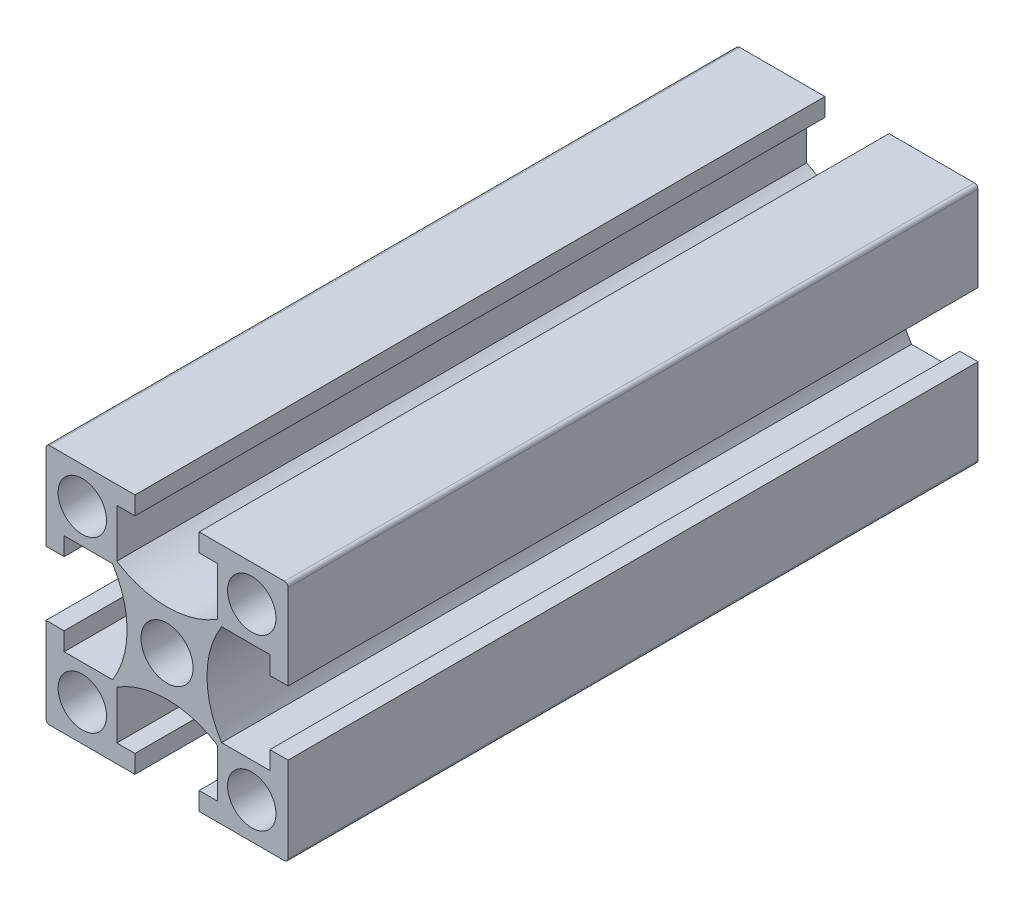
SolidWorks part; units mm, degrees
material "3.0255 (EN-AW 1350A)"
ref_plane "정면" through (0, 0, 0) normal (0, 0, 1) x (1, 0, 0)
ref_plane "윗면" through (0, 0, 0) normal (0, 1, 0) x (1, 0, 0)
ref_plane "우측면" through (0, 0, 0) normal (1, 0, 0) x (0, 0, -1)
sketch "스케치1" plane through (0, 0, 0) normal (0, 0, 1) x (1, 0, 0)
  line L0 (0, 32.0265) -> (0, -31.6588) construction
  line L1 (-10, 10) -> (-10, -10)
  line L2 (-10, 10) -> (10, 10)
  line L3 (-10, 2.65) -> (-8.5, 2.65)
  line L4 (13.6618, 0) -> (-11.6993, 0) construction
  line L5 (-8.5, 2.65) -> (-8.5, 4.15)
  line L6 (-8.5, 4.15) -> (-4.5032, 4.15)
  line L7 (-10, -2.65) -> (-8.5, -2.65)
  line L8 (-8.5, -2.65) -> (-8.5, -4.15)
  line L9 (-8.5, -4.15) -> (-4.5032, -4.15)
  line L10 (-10, -10) -> (10, -10)
  line L11 (10, 10) -> (10, -10)
  circle A0 centre (-7, 7) radius 2
  circle A1 centre (-7, -7) radius 2
  arc A2 (-4.5032, 4.15) -> (-4.5032, -4.15) centre (-11.0587, 0) cw
  circle A3 centre (0, 0) radius 2.15
  circle A4 centre (7, 7) radius 2
  circle A5 centre (7, -7) radius 2
  point P21 (-10, 0)
  point P23 (-3.3, 0)
  point P31 (0, -10)
  point P32 (0, 10)
  dimension "D3" = 4
  dimension "D9" = 6.7
  dimension "D10" = 4.3
  dimension "D11" = 7.7587
  dimension "D1" = 20
  dimension "D2" = 20
  dimension "D4" = 14
  dimension "D5" = 14
  dimension "D6" = 5.3
  dimension "D7" = 8.3
  dimension "D8" = 1.5
extrude "보스-돌출1" add sketch "스케치1" along normal blind 57 contours A0 | A4 | A3 | A5 | A1 | A2 L6 L5 L3 L1 L7 L8 L9 | L2 L11 L10 L1 region at (-6.6069, 0, 0) region at (-7, 7, 0) region at (-7, -7, 0) region at (0, 0, 0) region at (7, 7, 0) region at (7, -7, 0)
extrude "컷-돌출1" cut sketch "스케치1<3>" along normal up to next contours A2 L6 L5 L3 L1 L7 L8 L9 region at (-6.6069, 0, 0)
sketch "스케치1<3>" plane through (0, 0, 0) normal (0, 0, 1) x (1, 0, 0) same geometry as "스케치1"
pattern_circular "원형 패턴1" count 4 over 360 about axis through (0, 0, 57) along (0, 0, -1) of "컷-돌출1" reverse direction yes
fillet "필렛1" radius 0.3 4 edges at (10, -10, 28.5) (-10, -10, 28.5) (-10, 10, 28.5) (10, 10, 28.5)
sketch "스케치2" plane through (0, 0, 0) normal (1, 0, 0) x (0, 0, -1)
  line L0 (3.7612, 0) -> (-18.9549, 0) construction
  line L1 (0, -4.15) -> (0, 4.15) construction
  circle A0 centre (-19, 0) radius 2.5
  dimension "D1" = 5
  dimension "D2" = 19
extrude "컷-돌출2" cut sketch "스케치2" against normal through all both and the other way through all contours A0
sketch "스케치3" plane through (10, 0, 0) normal (1, 0, 0) x (0, 0, -1)
  line L0 (0, -2.65) -> (0, -9.7) construction
  circle A0 centre (-11, 0) radius 2.5
  dimension "D1" = 11
extrude "컷-돌출3" cut sketch "스케치3" against normal through all
sketch "스케치4" plane through (0, 10, 0) normal (0, 1, 0) x (1, 0, 0)
  line L0 (-4.15, -57) -> (4.15, -57) construction
  circle A0 centre (0, -48) radius 2.5
  dimension "D1" = 9
extrude "컷-돌출4" cut sketch "스케치4" against normal through all
